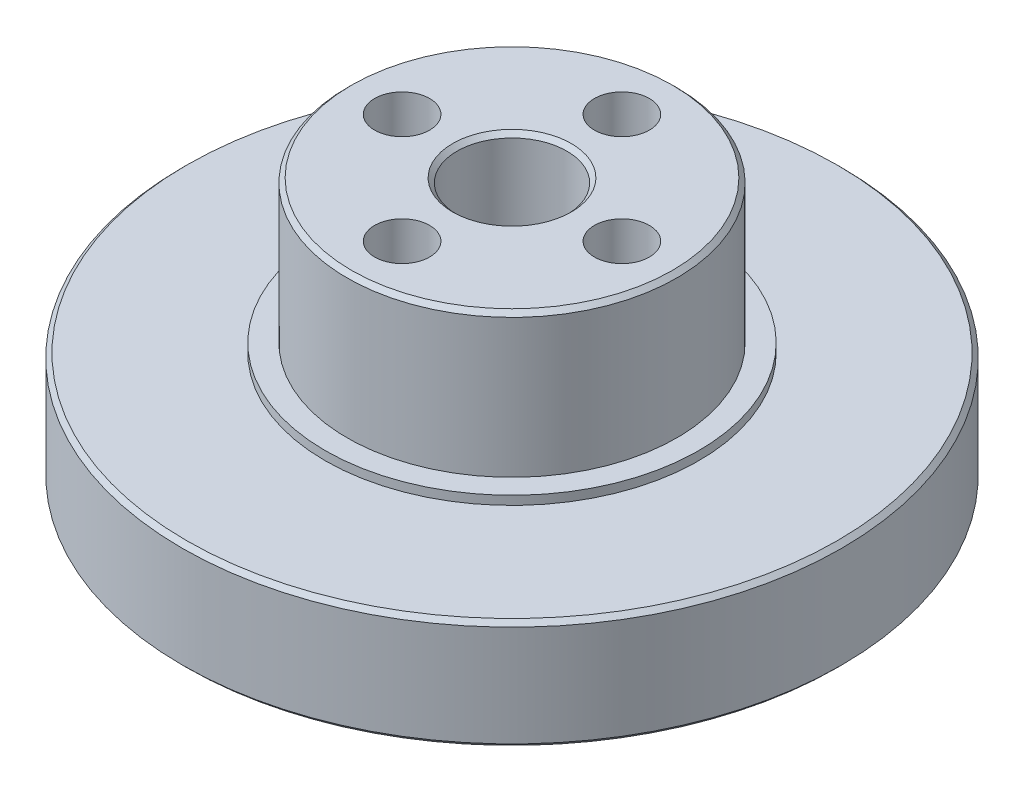
SolidWorks part; units mm, degrees
ref_plane "前视基准面" through (0, 0, 0) normal (0, 0, 1) x (1, 0, 0)
ref_plane "上视基准面" through (0, 0, 0) normal (0, 1, 0) x (1, 0, 0)
ref_plane "右视基准面" through (0, 0, 0) normal (1, 0, 0) x (0, 0, -1)
other "Configuration Table"
sketch "草图1" plane through (0, 0, 0) normal (0, 1, 0) x (1, 0, 0)
  circle A0 centre (0, 0) radius 11.525 construction
  circle A1 centre (0, 11.525) radius 1.83
  circle A2 centre (9.9809, 5.7625) radius 1.83
  circle A3 centre (9.9809, -5.7625) radius 1.83
  circle A4 centre (0, -11.525) radius 1.83
  circle A5 centre (-9.9809, -5.7625) radius 1.83
  circle A6 centre (-9.9809, 5.7625) radius 1.83
  circle A8 centre (0, 0) radius 15
  point P18 (0, 0)
  dimension "D1" = 23.05
  dimension "D2" = 3.66
  dimension "D5" = 30
  dimension "D3" = 6
extrude "凸台-拉伸1" add sketch "草图1" along normal blind 3.4
sketch "草图2" plane through (0, 3.4, 0) normal (0, 1, 0) x (1, 0, 0)
  circle A0 centre (0, 0) radius 15
extrude "凸台-拉伸2" add sketch "草图2" along normal blind 1.6
sketch "草图3" plane through (0, 5, 0) normal (0, 1, 0) x (1, 0, 0)
  circle A0 centre (0, 0) radius 8.5
  dimension "D1" = 17
extrude "凸台-拉伸3" add sketch "草图3" along normal blind 0.4
sketch "草图4" plane through (0, 5.4, 0) normal (0, 1, 0) x (1, 0, 0)
  circle A0 centre (0, 0) radius 7.5
  dimension "D1" = 15
extrude "凸台-拉伸4" add sketch "草图4" along normal blind 6.5
sketch "草图5" plane through (0, 11.9, 0) normal (0, 1, 0) x (1, 0, 0)
  circle A0 centre (0, 5) radius 1.25
  circle A1 centre (5, 0) radius 1.25
  circle A2 centre (0, -5) radius 1.25
  circle A3 centre (-5, 0) radius 1.25
  circle A4 centre (0, 0) radius 2.5
  point P12 (0, 0)
  dimension "D1" = 2.5
  dimension "D2" = 5
  dimension "D4" = 5
  dimension "D3" = 4
extrude "切除-拉伸1" cut sketch "草图5" against normal blind 5
chamfer "倒角1" distance 0.2 angle 45 10 edges at (-9.9809, 0, -3.9325) (-9.9809, 0, 7.5925) (0, 0, 13.355) (9.9809, 0, 7.5925) (9.9809, 0, -3.9325) (0, 0, -9.695) (0, 0, 15) (0, 11.9, 7.5) (0, 5, 15) (0, 11.9, 2.5)
sketch "草图7" plane through (0, 6.9, 0) normal (0, 1, 0) x (1, 0, 0)
  circle A2 centre (0, 0) radius 2.5 construction
  circle A3 centre (0, 0) radius 2.5
extrude "切除-拉伸4" cut sketch "草图7" against normal through all
sketch "草图8" plane through (0, 0, 0) normal (0, -1, 0) x (-1, 0, 0)
  circle A0 centre (0, 0) radius 6
  dimension "D1" = 6
extrude "切除-拉伸5" cut sketch "草图8" against normal blind 2
chamfer "倒角2" distance 0.5 angle 45 3 edges at (0, 0, -6) (0, 2, -2.5) (0, 2, -6)
